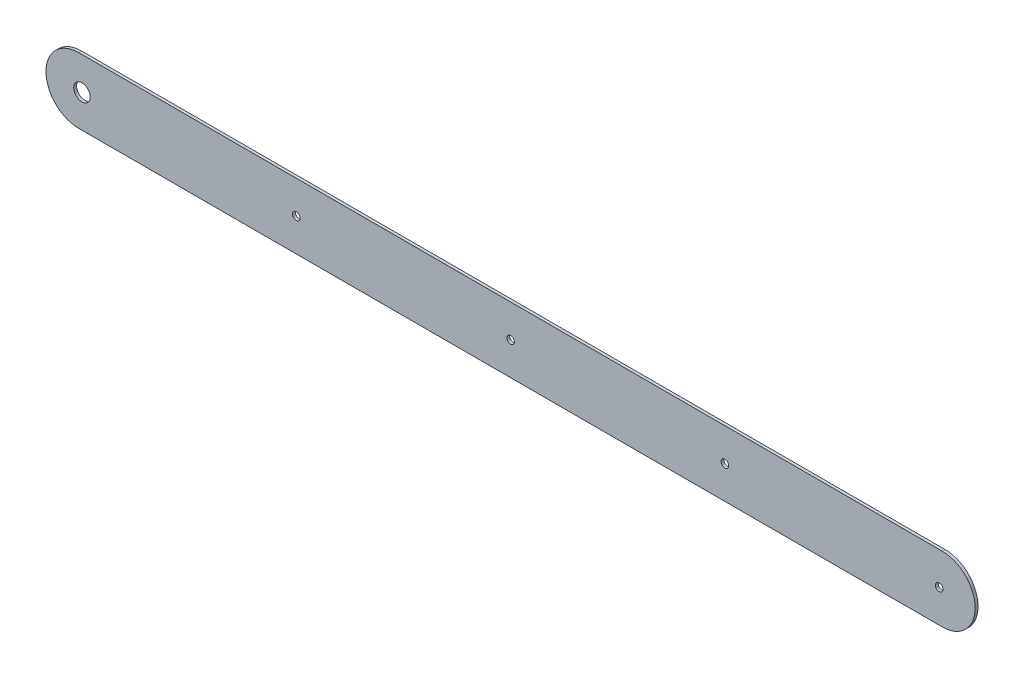
SolidWorks part; units mm, degrees
other "Weld Folder"
ref_plane "Front Plane" through (0, 0, 0) normal (0, 0, 1) x (1, 0, 0)
ref_plane "Top Plane" through (0, 0, 0) normal (0, 1, 0) x (1, 0, 0)
ref_plane "Right Plane" through (0, 0, 0) normal (1, 0, 0) x (0, 0, -1)
sketch "Sketch1" plane through (0, 0, 0) normal (0, 0, 1) x (1, 0, 0)
  line L1 (-914.4, 63.5) -> (914.4, 63.5)
  line L2 (-914.4, -63.5) -> (914.4, -63.5)
  arc A0 (-914.4, -63.5) -> (-914.4, 63.5) centre (-914.4, 0) cw
  arc A1 (914.4, -63.5) -> (914.4, 63.5) centre (914.4, 0) ccw
  point P4 (0, 0)
  point P8 (0, 63.5)
  point P11 (0, -63.5)
  dimension "D2" = 1828.8
extrude "Extrude-Thin1" add sketch "Sketch1" along normal mid plane 6 thin contours L2 A1 L1 A0 thin type one direction wall 6
extrude "Boss-Extrude1" add sketch "Sketch1<3>" along normal mid plane 6
sketch "Sketch1<3>" plane through (0, 0, 0) normal (0, 0, 1) x (1, 0, 0) same geometry as "Sketch1"
sketch "Sketch2" plane through (0, 0, 3) normal (0, 0, 1) x (1, 0, 0)
  circle A2 centre (0, 0) radius 8
  circle A3 centre (907.7, 0) radius 8
  circle A4 centre (-907.7, 0) radius 17.5
  circle A5 centre (453.85, 0) radius 8
  circle A6 centre (-453.85, 0) radius 8
  dimension "D1" = 35
  dimension "D2" = 16
extrude "Cut-Extrude1" cut sketch "Sketch2" against normal through all both and the other way through all
